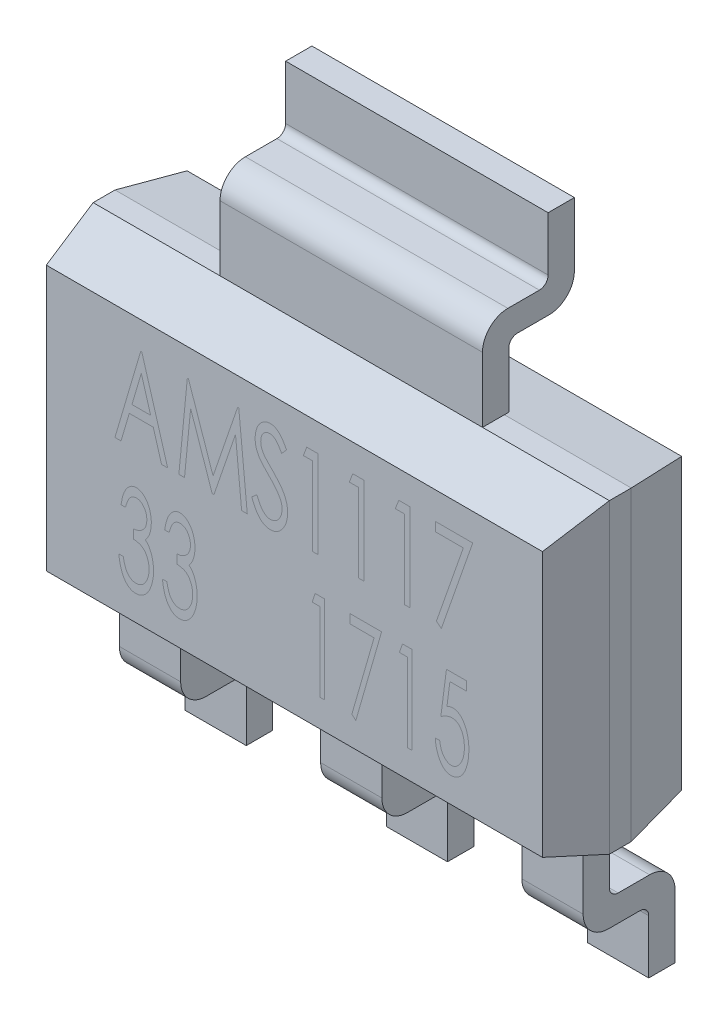
SolidWorks part; units mm, degrees
ref_plane "Alzado" through (0, 0, 0) normal (0, 0, 1) x (1, 0, 0)
ref_plane "Planta" through (0, 0, 0) normal (0, 1, 0) x (1, 0, 0)
ref_plane "Vista lateral" through (0, 0, 0) normal (1, 0, 0) x (0, 0, -1)
sketch "Croquis1" plane through (0, 0, 0) normal (0, 0, 1) x (1, 0, 0)
  line L0 (0, 0) -> (0, 3.5)
  line L1 (0, 3.5) -> (5.9, 3.5)
  line L2 (5.9, 3.5) -> (5.9, 0)
  line L3 (5.9, 0) -> (0, 0)
  dimension "D1" = 3.5
  dimension "D2" = 5.9
extrude "Saliente-Extruir1" add sketch "Croquis1" along normal blind 1.6
sketch "Croquis2" plane through (0, 3.5, 0) normal (0, 1, 0) x (1, 0, 0)
  line L0 (2.95, 0) -> (2.95, -1.6) construction
  line L1 (5.9, 0) -> (0, 0) construction
  line L2 (5.9, -1.6) -> (0, -1.6) construction
  line L3 (2.95, -0.4246) -> (4.45, -0.4246) construction
  line L4 (5.9, -1.6) -> (5.9, 0) construction
  line L5 (5.9, -0.8) -> (0, -0.8) construction
  line L6 (0, -1.6) -> (0, 0) construction
  line L7 (5.275, -0.8) -> (5.275, -0.65) construction
  line L8 (4.45, -0.65) -> (4.45, -0.95)
  line L9 (4.45, -0.95) -> (1.45, -0.95)
  line L10 (1.45, -0.95) -> (1.45, -0.65)
  line L11 (4.45, -0.65) -> (1.45, -0.65)
  dimension "D1" = 1.5
  dimension "D2" = 0.15
  dimension "D3" = 0.3
  dimension "D4" = 3
extrude "Saliente-Extruir2" add sketch "Croquis2" along normal blind 1.75
sketch "Croquis3" plane through (4.45, 0, 0) normal (1, 0, 0) x (0, 0, -1)
  line L0 (-0.65, 5.25) -> (0.1, 5.25) construction
  line L1 (-0.65, 4.375) -> (-0.65, 3.5) construction
  line L2 (-0.65, 5.25) -> (-0.65, 3.5) construction
  line L3 (-0.65, 3.9375) -> (0.1, 3.9375)
  line L4 (0.1, 3.9375) -> (0.1, 5.25)
  line L5 (0.1, 5.25) -> (-0.65, 5.25)
  line L6 (-0.65, 5.25) -> (-0.65, 3.9375)
  dimension "D1" = 0.75
extrude "Saliente-Extruir3" add sketch "Croquis3" against normal up to vertex (3 mm away) up to point (1.45, 5.25, 0.65)
sketch "Croquis4" plane through (4.45, 0, 0) normal (1, 0, 0) x (0, 0, -1)
  line L0 (0.1, 5.25) -> (-0.2, 5.25)
  line L1 (-0.95, 5.25) -> (0.1, 5.25) construction
  line L2 (-0.65, 3.9375) -> (-0.95, 3.9375)
  line L3 (-0.95, 5.25) -> (-0.95, 3.5) construction
  line L4 (-0.95, 3.9375) -> (-0.95, 4.2403)
  line L5 (-0.65, 3.9375) -> (-0.65, 4.1335)
  line L6 (-0.55, 4.2335) -> (-0.19, 4.2335)
  line L7 (0.1, 3.9375) -> (0.1, 5.25) construction
  line L8 (0.1, 4.5235) -> (0.1, 5.25)
  line L9 (-0.2, 5.25) -> (-0.2, 4.6335)
  line L10 (-0.3, 4.5335) -> (-0.66, 4.5335)
  line L11 (-0.95, 4.2435) -> (-0.95, 4.2403)
  line L12 (-0.2, 5.25) -> (-0.95, 5.25)
  line L13 (-0.95, 5.25) -> (-0.95, 3.9375)
  line L14 (0.1, 4.5235) -> (0.1, 3.9375)
  line L15 (0.1, 3.9375) -> (-0.65, 3.9375)
  arc A0 (-0.66, 4.5335) -> (-0.95, 4.2435) centre (-0.66, 4.2435) ccw
  arc A1 (-0.19, 4.2335) -> (0.1, 4.5235) centre (-0.19, 4.5235) ccw
  arc A2 (-0.2, 4.6335) -> (-0.3, 4.5335) centre (-0.3, 4.6335) cw
  arc A3 (-0.65, 4.1335) -> (-0.55, 4.2335) centre (-0.55, 4.1335) cw
  point P19 (-0.95, 4.5335)
  point P22 (0.1, 4.2335)
  line M16 (-0.65, 3.9375) -> (0.1, 3.9375)
  line M17 (0.1, 3.9375) -> (0.1, 5.25)
  line M18 (0.1, 5.25) -> (-0.95, 5.25)
  line M19 (-0.95, 5.25) -> (-0.95, 3.5)
  dimension "D4" = 0.29
  dimension "D5" = 0.1
  dimension "D1" = 0.3
  dimension "D2" = 0.3
  dimension "D3" = 0.3
extrude "Cortar-Extruir1" cut sketch "Croquis4" against normal blind 3 contours A2 L9 A0 L10 M18 M19 | A3 L5 A1 L6 M16 M17 region at (4.45, 4.8792, 0.5865) region at (4.45, 4.1005, 0.2483)
sketch "Croquis5" plane through (4.45, 0, 0) normal (1, 0, 0) x (0, 0, -1)
  line L0 (-1.6, 1.75) -> (0.2063, 1.75) construction
  line L1 (-1.6, 0) -> (-1.6, 3.5) construction
  line L2 (-0.95, 3.5) -> (-0.65, 3.5)
  line L3 (-0.65, 3.5) -> (-0.65, 4.1335)
  line L4 (-0.2, 5.25) -> (0.1, 5.25)
  line L5 (0.1, 5.25) -> (0.1, 4.5235)
  line L6 (-0.2, 5.25) -> (-0.2, 4.6335)
  line L7 (-0.95, 3.5) -> (-0.95, 4.2435)
  line L8 (-0.66, 4.5335) -> (-0.3, 4.5335)
  line L9 (-0.55, 4.2335) -> (-0.19, 4.2335)
  line L10 (-0.55, -0.7335) -> (-0.19, -0.7335)
  line L11 (-0.66, -1.0335) -> (-0.3, -1.0335)
  line L12 (-0.95, 0) -> (-0.95, -0.7435)
  line L13 (-0.2, -1.75) -> (-0.2, -1.1335)
  line L14 (0.1, -1.75) -> (0.1, -1.0235)
  line L15 (-0.2, -1.75) -> (0.1, -1.75)
  line L16 (-0.65, 0) -> (-0.65, -0.6335)
  line L17 (-0.95, 0) -> (-0.65, 0)
  arc A0 (-0.95, 4.2435) -> (-0.66, 4.5335) centre (-0.66, 4.2435) cw
  arc A1 (-0.65, 4.1335) -> (-0.55, 4.2335) centre (-0.55, 4.1335) cw
  arc A2 (-0.3, 4.5335) -> (-0.2, 4.6335) centre (-0.3, 4.6335) ccw
  arc A3 (-0.19, 4.2335) -> (0.1, 4.5235) centre (-0.19, 4.5235) ccw
  arc A4 (-0.19, -0.7335) -> (0.1, -1.0235) centre (-0.19, -1.0235) cw
  arc A5 (-0.3, -1.0335) -> (-0.2, -1.1335) centre (-0.3, -1.1335) cw
  arc A6 (-0.65, -0.6335) -> (-0.55, -0.7335) centre (-0.55, -0.6335) ccw
  arc A7 (-0.95, -0.7435) -> (-0.66, -1.0335) centre (-0.66, -0.7435) ccw
extrude "Saliente-Extruir4" add sketch "Croquis5" against normal blind 4.5 contours A4 L14 L15 L13 A5 L11 A7 L12 L17 L16 A6 L10
sketch "Croquis6" plane through (0, -1.75, 0) normal (0, -1, 0) x (1, 0, 0)
  line L0 (0, 1.6) -> (5.9, 1.6) construction
  line L1 (2.95, 1.6) -> (2.95, 0) construction
  line L2 (0.65, 1.6) -> (0.65, 0) construction
  line L3 (2.95, 1.2431) -> (3.3, 1.2431) construction
  line L4 (2.95, 1.009) -> (2.6, 1.009) construction
  line L6 (-0.05, -0.1) -> (4.45, -0.1) construction
  line L7 (2.6, -0.1) -> (3.3, -0.1)
  line L9 (2.6, 0.95) -> (3.3, 0.95)
  line L10 (0.3, 0.95) -> (1, 0.95)
  line L11 (0.65, 1.1392) -> (1, 1.1392) construction
  line L12 (0.65, 1.3588) -> (0.3, 1.3588) construction
  line L13 (0.3, 1.3588) -> (0.3, 1.1392)
  line L14 (0.3, -0.1) -> (1, -0.1)
  line L15 (1, -0.1) -> (1, 0.95)
  line L16 (1, 1.1392) -> (0.3, 1.1392)
  line L17 (2.6, 0.95) -> (2.6, -0.1)
  line L18 (3.3, 0.95) -> (3.3, -0.1)
  line L19 (0, 0.95) -> (4.45, 0.95) construction
  line L20 (0.3, 0.95) -> (0.3, -0.1)
  line L21 (2.6, 0.95) -> (1, 0.95)
  line L22 (1, -0.1) -> (2.6, -0.1)
  line L23 (0.3, 0.95) -> (-0.05, 0.95)
  line L24 (-0.05, 0.95) -> (-0.05, -0.1)
  line L25 (-0.05, -0.1) -> (0.3, -0.1)
  line L26 (3.3, 0.95) -> (3.953, 0.95)
  line L27 (3.953, 0.95) -> (3.953, -0.1)
  line L28 (3.953, -0.1) -> (3.3, -0.1)
  line M8 (4.45, 0.2) -> (-0.05, 0.2)
  line M9 (-0.05, 0.2) -> (-0.05, -0.1)
  line M10 (-0.05, -0.1) -> (4.45, -0.1)
  dimension "D1" = 2.3
  dimension "D2" = 0.35
  dimension "D3" = 0.35
  dimension "D4" = 0.35
  dimension "D5" = 0.35
extrude "Cortar-Extruir2" cut sketch "Croquis6" against normal blind 1.75 contours L17 L21 L15 M8 | L17 L15 M8 M10 | L23 L24 L20 M8 | L20 M8 M9 M10 | L27 L26 L18 M8 | L27 L18 M8 M10 region at (1.8, -1.75, 0.05) region at (3.6265, -1.75, 0.05) region at (1.8, -1.75, 0.575) region at (3.6265, -1.75, 0.575) region at (0.125, -1.75, 0.05) region at (0.125, -1.75, 0.575)
sketch "Croquis7" plane through (4.45, 0, 0) normal (1, 0, 0) x (0, 0, -1)
  line L0 (-0.95, 0) -> (-0.95, -0.7435)
  line L1 (-0.95, 0) -> (-0.65, 0)
  line L2 (-0.65, 0) -> (-0.65, -0.6335)
  line L3 (-0.19, -0.7335) -> (-0.55, -0.7335)
  line L4 (-0.66, -1.0335) -> (-0.3, -1.0335)
  line L5 (-0.2, -1.1335) -> (-0.2, -1.75)
  line L6 (-0.2, -1.75) -> (0.1, -1.75)
  line L7 (0.1, -1.75) -> (0.1, -1.0235)
  arc A0 (-0.95, -0.7435) -> (-0.66, -1.0335) centre (-0.66, -0.7435) ccw
  arc A1 (-0.65, -0.6335) -> (-0.55, -0.7335) centre (-0.55, -0.6335) ccw
  arc A2 (-0.2, -1.1335) -> (-0.3, -1.0335) centre (-0.3, -1.1335) ccw
  arc A3 (-0.19, -0.7335) -> (0.1, -1.0235) centre (-0.19, -1.0235) cw
extrude "Saliente-Extruir6" add sketch "Croquis7" along normal blind 1.4
sketch "Croquis8" plane through (0, -1.75, 0) normal (0, -1, 0) x (1, 0, 0)
  line L0 (2.95, -0.1) -> (5.25, -0.1) construction
  line L1 (2.6, -0.1) -> (3.3, -0.1) construction
  line L2 (3.953, -0.1) -> (5.85, -0.1) construction
  line L3 (5.25, -0.1) -> (5.25, 0.95) construction
  line L4 (3.953, 0.95) -> (5.85, 0.95) construction
  line L5 (5.25, 0.95) -> (4.9, 0.95) construction
  line L6 (5.25, 0.95) -> (5.6, 0.95) construction
  line L7 (4.9, 0.95) -> (4.9, -0.1)
  line L8 (4.9, -0.1) -> (5.6, -0.1)
  line L9 (5.6, -0.1) -> (5.6, 0.95)
  line L10 (5.6, 0.95) -> (4.9, 0.95)
  line L11 (4.9, 0.95) -> (3.953, 0.95)
  line L12 (3.953, 0.95) -> (3.953, -0.1)
  line L13 (3.953, -0.1) -> (4.9, -0.1)
  line L14 (5.6, -0.1) -> (5.85, -0.1)
  line L15 (5.85, -0.1) -> (5.85, 0.95)
  line L16 (5.85, 0.95) -> (5.6, 0.95)
  dimension "D1" = 2.3
  dimension "D2" = 0.35
  dimension "D3" = 0.35
extrude "Cortar-Extruir3" cut sketch "Croquis8" against normal blind 1.75 contours L12 L13 L7 L11 | L15 L16 L9 L14 region at (4.4265, -1.75, 0.425) region at (5.725, -1.75, 0.425)
sketch "Croquis9" plane through (0, 0, 0) normal (-1, 0, 0) x (0, 0, 1)
  line L1 (0.95, 0) -> (1.6, 0.2366)
  line L2 (1.6, 3.5) -> (1.6, 0) construction
  line L3 (0.95, 3.5) -> (1.6, 3.2634)
  line L4 (1.6, 3.5) -> (0, 3.5) construction
  line L5 (1.6, 0) -> (0, 0) construction
  line L6 (1.6, 3.2634) -> (1.6, 0.2366)
  line L7 (0.95, 3.5) -> (0.7, 3.5)
  line L8 (0.65, 3.5) -> (0.95, 3.5) construction
  line L9 (0.7, 3.5) -> (0, 3.4016)
  line L10 (0, 3.5) -> (0, 0) construction
  line L11 (0.7, 0) -> (0, 0.0984)
  line L12 (0, 3.4016) -> (0, 0.0984)
  line L13 (1.6, 3.5) -> (0, 3.5)
  line L14 (0, 3.5) -> (0, 3.4016)
  line L15 (1.6, 3.5) -> (1.6, 3.2634)
  line L16 (1.6, 0.2366) -> (1.6, 0)
  line L17 (1.6, 0) -> (0.95, 0)
  line L18 (0.95, 0) -> (0, 0)
  line L19 (0, 0) -> (0, 0.0984)
  line M6 (0, 3.5) -> (0, 0)
  line M7 (0, 0) -> (1.6, 0)
  line M8 (1.6, 0) -> (1.6, 3.5)
  line M9 (1.6, 3.5) -> (0, 3.5)
  dimension "D1" = 20
  dimension "D2" = 20
  dimension "D3" = 0.25
  dimension "D4" = 8
  dimension "D5" = 8
extrude "Cortar-Extruir4" cut sketch "Croquis9" against normal blind 5.9 contours L3 M9 M8 | L9 M9 M6 | L1 M7 M8 | L11 M7 M6 region at (0, 0.0789, 1.3833) region at (0, 0.0328, 0.2333) region at (0, 3.4211, 1.3833) region at (0, 3.4672, 0.2333)
sketch "Croquis11" plane through (0, 3.5, 0) normal (0, 1, 0) x (1, 0, 0)
  line L0 (0, -0.7) -> (0.1234, 0)
  line L1 (5.9, 0) -> (0, 0) construction
  line L2 (0, -0.7) -> (0, 0) construction
  line L3 (0, -0.95) -> (0.1146, -1.6)
  line L4 (5.9, -1.6) -> (0, -1.6) construction
  line L5 (0, -0.95) -> (0, -1.6) construction
  line L6 (0.1234, 0) -> (0, 0)
  line L7 (0, 0) -> (0, -0.7)
  line L8 (0, -0.7) -> (0, -1.6)
  line L9 (0, -1.6) -> (0.1146, -1.6)
  line L10 (2.95, -1.6) -> (2.95, 0.1) construction
  line L11 (1.45, 0.1) -> (4.45, 0.1) construction
  line L12 (5.9, -1.6) -> (5.7854, -1.6)
  line L13 (5.9, -0.7) -> (5.9, -1.6)
  line L14 (5.9, 0) -> (5.9, -0.7)
  line L15 (5.7766, 0) -> (5.9, 0)
  line L16 (5.9, -0.95) -> (5.7854, -1.6)
  line L17 (5.9, -0.7) -> (5.7766, 0)
  dimension "D1" = 10
  dimension "D2" = 10
extrude "Cortar-Extruir5" cut sketch "Croquis11" against normal blind 3.5 contours L6 L7 L0 | L8 L9 L3 | L13 L16 L12 | L17 L14 L15 region at (0.0411, 3.5, 0.2333) region at (0.0382, 3.5, 1.3833) region at (5.8589, 3.5, 0.2333) region at (5.8618, 3.5, 1.3833)
sketch "Croquis12" plane through (0, 0, 1.6) normal (0, 0, 1) x (1, 0, 0)
  line L0 (5.7854, 3.2634) -> (5.7854, 1.75) construction
  line L1 (5.7854, 0.2366) -> (5.7854, 3.2634) construction
  line L2 (5.7854, 1.75) -> (0.1146, 1.75) construction
  line L3 (0.1146, 0.2366) -> (0.1146, 3.2634) construction
  line L4 (0.1146, 1.75) -> (0.1146, 1.95) construction
  line L5 (0.1146, 1.75) -> (0.1146, 1.55) construction
  line L6 (0.1146, 1.95) -> (5.7854, 1.95) construction
  line L7 (0.1146, 1.55) -> (5.7854, 1.55) construction
  line L8 (0.1146, 1.55) -> (0.1146, 0.55) construction
  line L9 (0.1146, 0.55) -> (5.7854, 0.55) construction
  text T0 "AMS1117" font "Century Gothic" height 1
  text T1 "33    1715" font "Century Gothic" height 1
  dimension "D1" = 0.2
  dimension "D2" = 0.2
  dimension "D3" = 1
wrap "Envolver1" sketch "Croquis12" wrap type scribe source sketch "Croquis12" face at (2.95, 1.75, 1.6)
